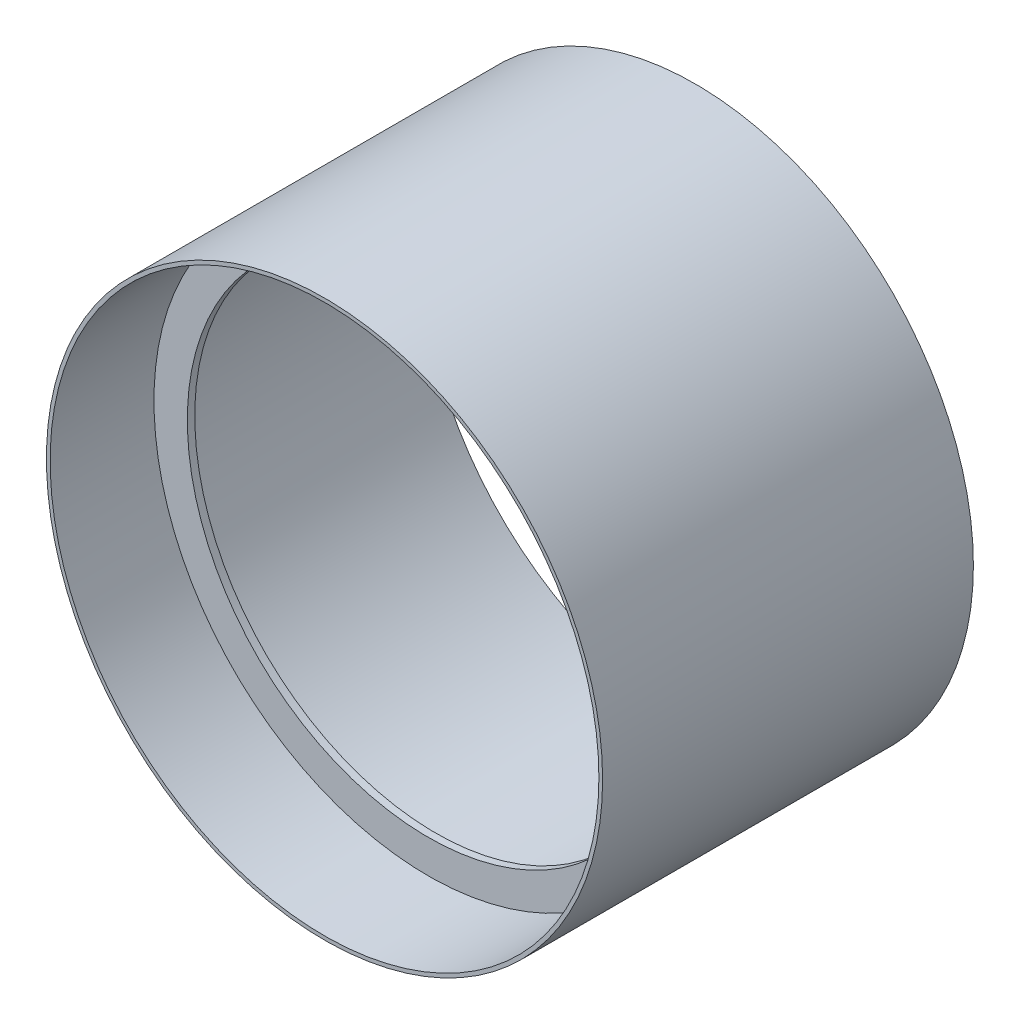
SolidWorks part; units mm, degrees
ref_plane "前视基准面" through (0, 0, 0) normal (0, 0, 1) x (1, 0, 0)
ref_plane "上视基准面" through (0, 0, 0) normal (0, 1, 0) x (1, 0, 0)
ref_plane "右视基准面" through (0, 0, 0) normal (1, 0, 0) x (0, 0, -1)
sketch "草图1" plane through (0, 0, 0) normal (0, 0, 1) x (1, 0, 0)
  circle A0 centre (0, 0) radius 75
  dimension "D1" = 150
extrude "凸台-拉伸1" add sketch "草图1" along normal blind 100
shell "抽壳1" thickness 1 removed face at (75, 0, 0) removed face at (75, 0, 100)
ref_plane "基准面1" through (0, 0, 70) normal (0, 0, 1) x (1, 0, 0)
sketch "草图2" plane through (0, 0, 70) normal (0, 0, 1) x (1, 0, 0)
  circle A0 centre (0, 0) radius 75
  circle A1 centre (0, 0) radius 65
  dimension "D1" = 150
  dimension "D2" = 130
extrude "凸台-拉伸2" add sketch "草图2" along normal blind 2
